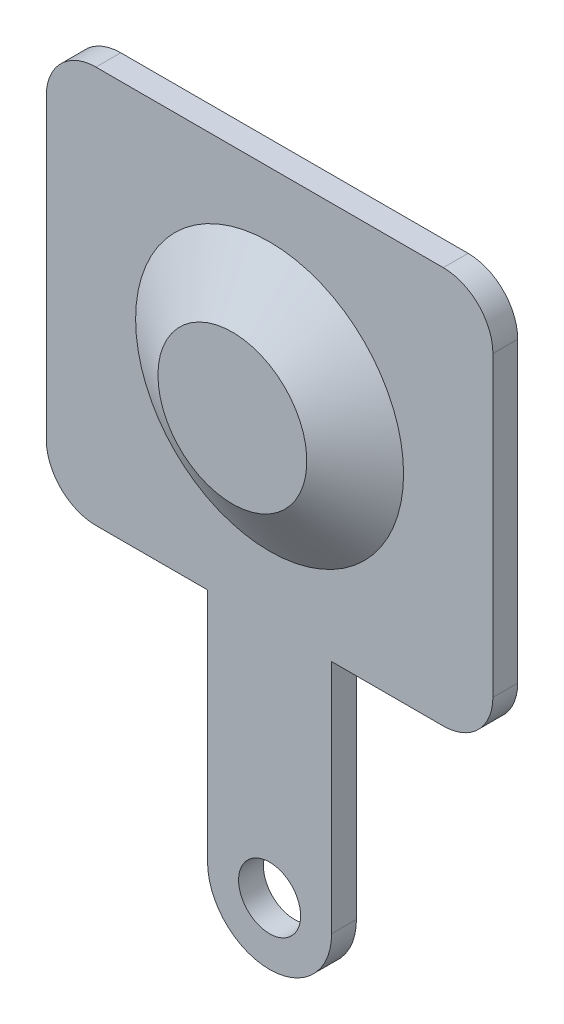
SolidWorks part; units mm, degrees
ref_plane "Front Plane" through (0, 0, 0) normal (0, 0, 1) x (1, 0, 0)
ref_plane "Top Plane" through (0, 0, 0) normal (0, 1, 0) x (1, 0, 0)
ref_plane "Right Plane" through (0, 0, 0) normal (1, 0, 0) x (0, 0, -1)
ref_axis "X-Axis" through (-88.99, 0, 0) along (1, 0, 0)
ref_axis "Y-Axis" through (0, 55, 0) along (0, -1, 0)
ref_axis "Z-Axis" through (0, 0, -88.99) along (0, 0, 1)
sketch "Sketch1" plane through (0, 0, 0) normal (0, 0, 1) x (1, 0, 0)
  line L1 (-4.5, -4) -> (4.5, -4)
  line L2 (-4.5, -4) -> (-4.5, 4)
  line L3 (-4.5, 4) -> (4.5, 4)
  line L4 (4.5, -4) -> (4.5, 4)
  line L5 (-4.5, -4) -> (4.5, 4) construction
  line L6 (-4.5, 4) -> (4.5, -4) construction
  point P0 (0, 0)
  dimension "D1" = 8
  dimension "D2" = 9
extrude "Boss-Extrude1" add sketch "Sketch1" along normal blind 0.5
sketch "Sketch2" plane through (0, 0, 0) normal (0, 0, 1) x (1, 0, 0)
  line L0 (0, 0) -> (0, -8.75) construction
  line L1 (1.25, 0) -> (1.25, -8.75)
  line L2 (-1.25, 0) -> (-1.25, -8.75)
  line L4 (4.5, 4) -> (-4.5, 4) construction
  arc A0 (1.25, 0) -> (-1.25, 0) centre (0, 0) ccw
  arc A1 (-1.25, -8.75) -> (1.25, -8.75) centre (0, -8.75) ccw
  point P3 (0, -4.375)
  dimension "D2" = 1.25
  dimension "D1" = 12.75
extrude "Boss-Extrude2" add sketch "Sketch2" along normal up to surface (0.5 mm away) up to face at (0, 0, 0.5)
fillet "Fillet1" radius 1 4 edges at (-4.5, 4, 0.25) (4.5, 4, 0.25) (4.5, -4, 0.25) (-4.5, -4, 0.25)
sketch "Sketch4" plane through (0, 0, 0.5) normal (0, 0, 1) x (1, 0, 0)
  line L0 (-1.25, -8.75) -> (1.25, -8.75) construction
  circle A0 centre (0, -8.75) radius 0.625
  dimension "D1" = 1.25
extrude "Cut-Extrude1" cut sketch "Sketch4" against normal through all
sketch "Sketch5" plane through (0, 0, 0) normal (0, 1, 0) x (1, 0, 0)
  line L0 (0, -0.5) -> (2.7, -0.5)
  line L1 (3.5, -0.5) -> (-3.5, -0.5) construction
  line L2 (2.7, -0.5) -> (1.5, -1.25)
  line L3 (1.5, -1.25) -> (0, -1.25)
  line L4 (0, -1.25) -> (0, -0.5)
  dimension "D1" = 0.75
  dimension "D2" = 1.5
  dimension "D3" = 2.7
revolve "Revolve1" add sketch "Sketch5" angle 360 about axis through (0, 0, -88.99) along (0, 0, 1)
shell "Shell1" thickness 0.5 removed face at (0.625, -8.75, 0)
equation "\"D1@Sketch2\"=14-\"D2@Sketch2\""
equation "\"D1@Shell1\"=\"D1@Boss-Extrude1\""
